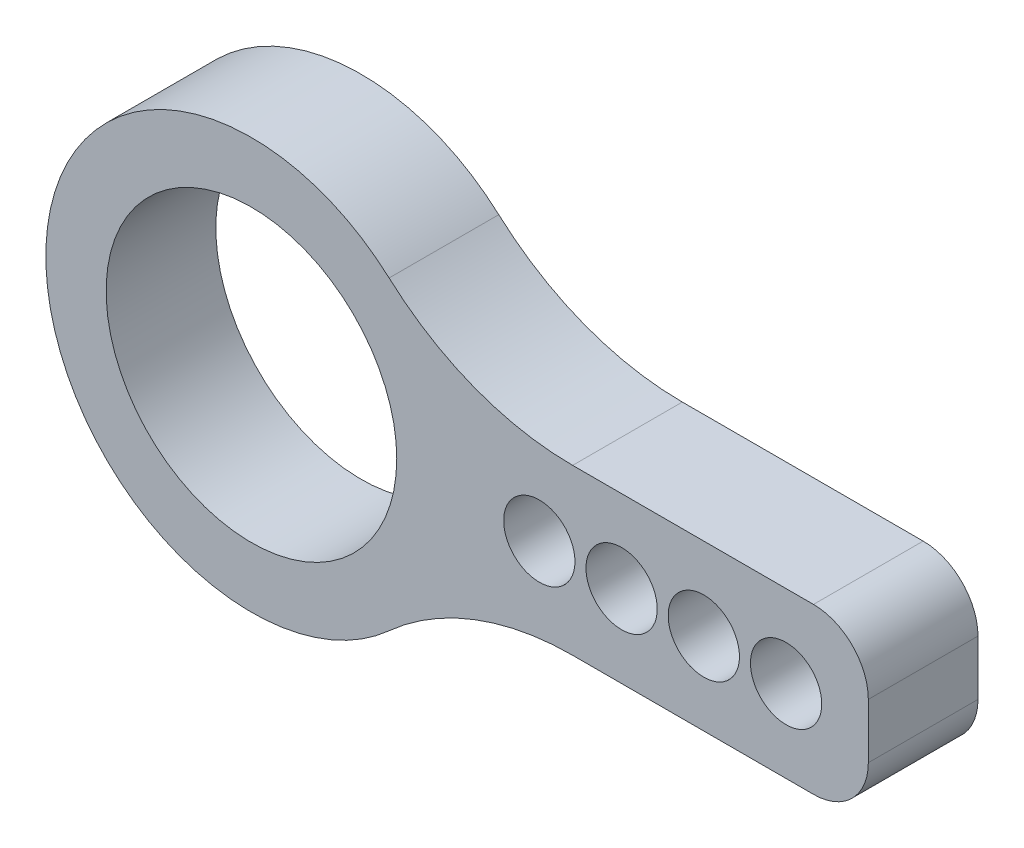
SolidWorks part; units mm, degrees
ref_plane "正面" through (0, 0, 0) normal (0, 0, 1) x (1, 0, 0)
ref_plane "平面" through (0, 0, 0) normal (0, 1, 0) x (1, 0, 0)
ref_plane "右側面" through (0, 0, 0) normal (1, 0, 0) x (0, 0, -1)
sketch "ｽｹｯﾁ1" plane through (0, 0, 0) normal (0, 0, 1) x (1, 0, 0)
  line L1 (-4.5, -3) -> (-30, -3)
  line L2 (-4.5, -3) -> (-4.5, 3)
  line L3 (-4.5, 3) -> (-30, 3)
  line L4 (-30, -3) -> (-30, 3)
  circle A0 centre (-7.5, 0) radius 0.65 construction
  circle A2 centre (-7.5, 0) radius 0.65 construction
  circle A3 centre (-7.5, 0) radius 1.3
  circle A4 centre (-13.5, 0) radius 1.3
  circle A5 centre (-16.5, 0) radius 1.3
  circle A6 centre (-10.5, 0) radius 1.3
  circle A7 centre (-27, 0) radius 7.5
  circle A8 centre (-27, 0) radius 5.3
  circle A9 centre (0, 0) radius 1.25 construction
  point P9 (-4.5, 0)
  dimension "D1" = 3
  dimension "D3" = 0
  dimension "D5" = 2.6
  dimension "D6" = 15
  dimension "D9" = 10.6
  dimension "D2" = 30
  dimension "D4" = 6
  dimension "D7" = 3
  dimension "D8" = 3
extrude "ﾎﾞｽ - 押し出し1" add sketch "ｽｹｯﾁ1" along normal blind 4 contours A8 L1 A7 L3 | A8 L3 A7 L1 | A7 L1 L2 L3 A6 A5 A4 A3 region at (-12.1351, 0, 0) region at (-34.2922, 0, 0) region at (-20.8606, 0, 0)
fillet "ﾌｨﾚｯﾄ1" radius 10 2 edges at (-20.1261, 3, 2) (-20.1261, -3, 2)
fillet "ﾌｨﾚｯﾄ2" radius 2 2 edges at (-4.5, 3, 2) (-4.5, -3, 2)
